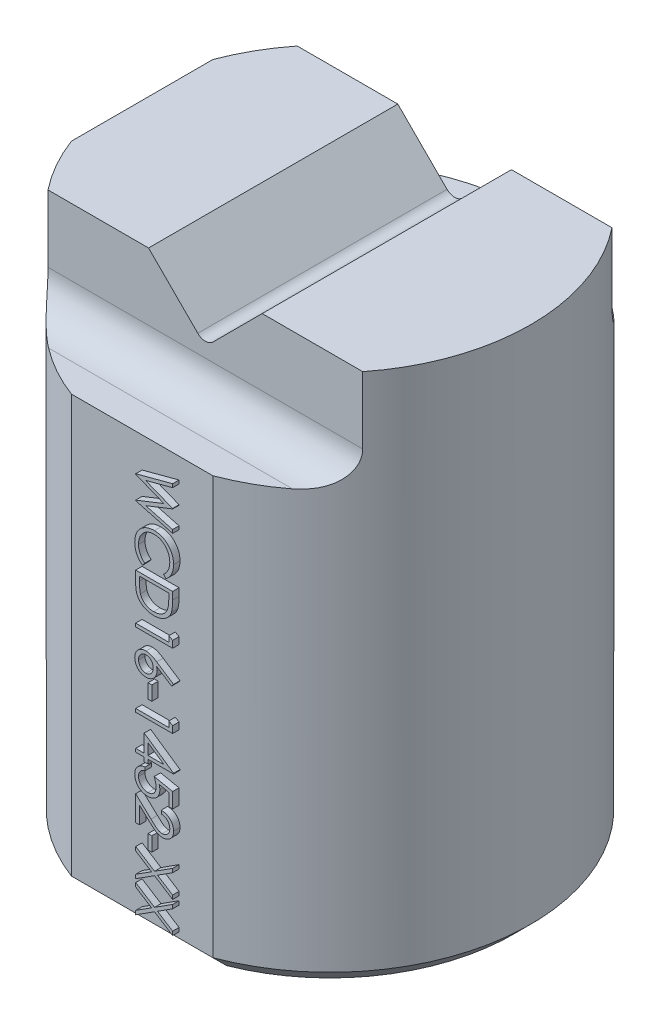
SolidWorks part; units mm, degrees
material "S7"
ref_plane "Alzado" through (0, 0, 0) normal (0, 0, 1) x (1, 0, 0)
ref_plane "Planta" through (0, 0, 0) normal (0, 1, 0) x (1, 0, 0)
ref_plane "Vista lateral" through (0, 0, 0) normal (1, 0, 0) x (0, 0, -1)
sketch "Croquis3" plane through (0, 0, 0) normal (0, 1, 0) x (1, 0, 0)
  circle A0 centre (0, 0) radius 19.0246
  dimension "D1" = 38.0492
extrude "Saliente-Extruir1" add sketch "Croquis3" along normal blind 50.8
sketch "Croquis7" plane through (0, 0, 0) normal (1, 0, 0) x (0, 0, -1)
  line L0 (-19.0246, 50.8) -> (-19.0246, 0) construction
  line L3 (0, 0) -> (0, 50.8) construction
  line L5 (19.0246, 50.8) -> (-19.0246, 50.8) construction
  line L7 (11.811, 50.8) -> (-11.811, 50.8) construction
  line L9 (19.0246, 50.8) -> (19.0246, 41.148)
  line L14 (15.113, 41.148) -> (19.0246, 41.148)
  line L15 (11.811, 50.8) -> (11.811, 44.45)
  line L16 (-11.811, 50.8) -> (-19.0246, 50.8)
  line L17 (-11.811, 50.8) -> (-11.811, 44.45)
  line L18 (-15.113, 41.148) -> (-19.0246, 41.148)
  line L19 (-19.0246, 50.8) -> (-19.0246, 41.148)
  line L20 (11.811, 50.8) -> (19.0246, 50.8)
  arc A0 (-11.811, 44.45) -> (-15.113, 41.148) centre (-15.113, 44.45) cw
  arc A2 (11.811, 44.45) -> (15.113, 41.148) centre (15.113, 44.45) ccw
  dimension "D3" = 3.302
  dimension "D1" = 23.622
  dimension "D2" = 9.652
extrude "Cortar-Extruir2" cut sketch "Croquis7" against normal blind 58.42 and the other way blind 58.42
sketch "Croquis9" plane through (0, 0, 0) normal (0, 0, 1) x (1, 0, 0)
  line L0 (0, 46.852) -> (0, 50.8034) construction
  line L2 (-14.9143, 50.8) -> (14.9143, 50.8) construction
  line L3 (0, 46.852) -> (0, 0) construction
  line L6 (-5.3848, 50.8) -> (-0.7184, 46.1336)
  line L7 (0.7184, 46.1336) -> (5.3848, 50.8)
  line L8 (-5.3848, 50.8) -> (5.3848, 50.8)
  circle A0 centre (0, 50.8034) radius 3.81 construction
  arc A1 (-0.7184, 46.1336) -> (0.7184, 46.1336) centre (0, 46.852) ccw
  dimension "D1" = 1.016
  dimension "D3" = 7.62
  dimension "D2" = 90
  dimension "D4" = 10.7696
extrude "Cortar-Extruir4" cut sketch "Croquis9" against normal blind 58.42 and the other way blind 58.42 contours L8 A0 | L6 A1 L7 L8
sketch "Croquis4" plane through (0, 50.8, 0) normal (0, 1, 0) x (1, 0, 0)
  line L0 (0, -19.0246) -> (0, -17.8054) construction
  line L1 (0, -17.8054) -> (-6.701, -17.8054)
  line L2 (0, -17.8054) -> (6.701, -17.8054)
  line L3 (-19.0246, 0) -> (-17.8054, 0) construction
  line L4 (-17.8054, 0) -> (-17.8054, -6.701)
  line L5 (-17.8054, 0) -> (-17.8054, 6.701)
  circle A1 centre (0, 0) radius 19.0246 construction
  arc A2 (-6.701, -17.8054) -> (6.701, -17.8054) centre (0, 0) ccw
  arc A3 (-17.8054, -6.701) -> (-17.8054, 6.701) centre (0, 0) cw
  dimension "D1" = 1.2192
  dimension "D2" = 1.2192
extrude "Cortar-Extruir1" cut sketch "Croquis4" against normal blind 58.42
sketch "Croquis12" plane through (0, 0, 0) normal (0, 0, 1) x (1, 0, 0)
  line L0 (0, 0) -> (0, 41.148) construction
  line L1 (-6.701, 41.148) -> (6.701, 41.148) construction
  text T0 "WCD16-1452-XX"
extrude "Saliente-Extruir2" add sketch "Croquis12" along normal blind 18.415
chamfer "Chaflán1" distance 1.5875 angle 45 4 edges at (-17.8054, 0, 0) (-13.4524, 0, 13.4524) (0, 0, 17.8054) (13.4524, 0, -13.4524)
